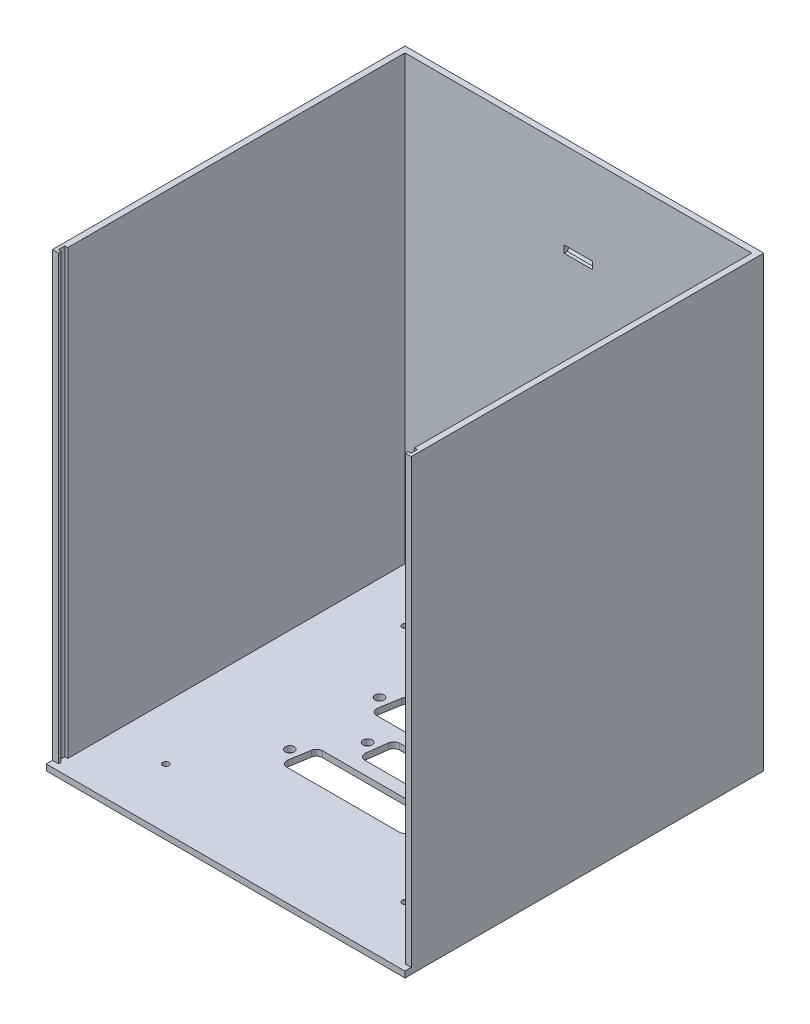
SolidWorks part; units mm, degrees
other "Markup1"
sketch "Sketch8" plane through (60, 0, -60) normal (0.7052, -0.7014, -0.1039) x (0.274, 0.4048, -0.8724)
other "Markup2"
sketch "Sketch9" plane through (60, 0, -60) normal (0.9922, -0.0018, -0.1244) x (-0.0942, 0.6423, -0.7606)
ref_plane "Front Plane" through (0, 0, 0) normal (0, 0, 1) x (1, 0, 0)
ref_plane "Top Plane" through (0, 0, 0) normal (0, 1, 0) x (1, 0, 0)
ref_plane "Right Plane" through (0, 0, 0) normal (1, 0, 0) x (0, 0, -1)
sketch "Sketch1" plane through (0, 0, 0) normal (0, 1, 0) x (1, 0, 0)
  line L5 (-60, 60) -> (60, 60)
  line L6 (-60, 60) -> (-60, -60)
  line L7 (-60, -60) -> (60, -60)
  line L8 (60, 60) -> (60, -60)
  dimension "D1" = 120
  dimension "D2" = 120
  dimension "D3" = 60
  dimension "D4" = 60
extrude "Main-Body" add sketch "Sketch1" along normal blind 150
sketch "Sketch11" plane through (0, 150, 0) normal (0, 1, 0) x (1, 0, 0)
  line L0 (-60, 60) -> (-60, -60) construction
  line L1 (58, -60) -> (-58, -60)
  line L2 (58, -60) -> (58, 58)
  line L3 (58, 58) -> (-58, 58)
  line L4 (-58, -60) -> (-58, 58)
  line L5 (58, -60) -> (-58, 58) construction
  line L6 (58, 58) -> (-58, -60) construction
  line L13 (60, 60) -> (-60, 60) construction
  point P0 (0, -1)
  dimension "D1" = 116
  dimension "D2" = 118
  dimension "D6" = 2
  dimension "D7" = 2
extrude "Hollow" cut sketch "Sketch11" against normal blind 148
sketch "Sketch12" plane through (0, 150, 0) normal (0, 1, 0) x (1, 0, 0)
  line L0 (-60, 60) -> (-60, -60) construction
  line L1 (-58, -60) -> (-60, -60)
  line L2 (-58, -60) -> (-58, -57.9)
  line L3 (-58, -57.9) -> (-60, -57.9)
  line L4 (-60, -60) -> (-60, -57.9)
  dimension "D1" = 2.1
extrude "Lid-Cut" cut sketch "Sketch12" against normal blind 148
mirror "Mirror-Lid-Cut" about plane through (0, 0, 0) normal (1, 0, 0) of "Lid-Cut"
sketch "Sketch13" plane through (0, 150, 0) normal (0, 1, 0) x (1, 0, 0)
  line L0 (-58, 58) -> (-58, -57.9) construction
  line L1 (-58, -57) -> (-59, -57)
  line L2 (-58, -57) -> (-58, -54.8)
  line L3 (-58, -54.8) -> (-59, -54.8)
  line L4 (-59, -57) -> (-59, -54.8)
  line L5 (-58, -57.9) -> (-60, -57.9) construction
  dimension "D1" = 1
  dimension "D2" = 0.9
  dimension "D3" = 2.2
extrude "Rail-Cut" cut sketch "Sketch13" against normal blind 148
mirror "Mirror-Rail-Cut" about plane through (0, 0, 0) normal (1, 0, 0) of "Rail-Cut"
sketch "Sketch2" plane through (0, 0, 0) normal (0, -1, 0) x (1, 0, 0)
  circle A0 centre (-40, 40) radius 1
  circle A1 centre (40, 40) radius 1
  circle A2 centre (40, -40) radius 1
  circle A3 centre (-40, -40) radius 1
  dimension "D1" = 40
  dimension "D3" = 2
  dimension "D2" = 40
  dimension "D4" = 2
  dimension "D5" = 2
extrude "Main-PCB-Holes" cut sketch "Sketch2" against normal up to next
sketch "Sketch4" plane through (0, 0, 0) normal (0, -1, 0) x (1, 0, 0)
  line L0 (-12.5, 0) -> (12.5, 0) construction
  line L1 (-23.52, -15) -> (23.52, -15) construction
  line L2 (-6.8916, -5.1179) -> (6.8916, -5.1179)
  line L4 (-7.7666, 5.6321) -> (7.7666, 5.6321)
  line L6 (-17.6522, -20.0462) -> (17.6522, -20.0462)
  line L8 (-18.7772, -9.2962) -> (18.7772, -9.2962)
  line L10 (-23.52, 15) -> (23.52, 15) construction
  line L11 (-17.6522, 9.9538) -> (17.6522, 9.9538)
  line L13 (-18.7772, 20.7038) -> (18.7772, 20.7038)
  line L16 (-19.625, 11.625) -> (-20.75, 18.375)
  line L19 (20.75, 18.375) -> (19.625, 11.625)
  line L22 (-8.875, -3.375) -> (-9.75, 3.375)
  line L25 (9.75, 3.375) -> (8.875, -3.375)
  line L28 (-20.75, -11.625) -> (-19.625, -18.375)
  line L31 (19.625, -18.375) -> (20.75, -11.625)
  circle A0 centre (-12.5, 0) radius 1.5
  circle A1 centre (12.5, 0) radius 1.5
  circle A2 centre (-23.52, -15) radius 1.5
  circle A3 centre (23.52, -15) radius 1.5
  circle A4 centre (-23.52, 15) radius 1.5
  circle A5 centre (23.52, 15) radius 1.5
  arc A6 (18.7772, 20.7038) -> (20.75, 18.375) centre (18.7772, 18.7038) cw
  arc A7 (-18.7772, 20.7038) -> (-20.75, 18.375) centre (-18.7772, 18.7038) ccw
  arc A8 (17.6522, 9.9538) -> (19.625, 11.625) centre (17.6522, 11.9538) ccw
  arc A9 (-17.6522, 9.9538) -> (-19.625, 11.625) centre (-17.6522, 11.9538) cw
  arc A10 (20.75, -11.625) -> (18.7772, -9.2962) centre (18.7772, -11.2962) ccw
  arc A11 (17.6522, -20.0462) -> (19.625, -18.375) centre (17.6522, -18.0462) ccw
  arc A12 (-19.625, -18.375) -> (-17.6522, -20.0462) centre (-17.6522, -18.0462) ccw
  arc A13 (-20.75, -11.625) -> (-18.7772, -9.2962) centre (-18.7772, -11.2962) cw
  arc A14 (7.7666, 5.6321) -> (9.75, 3.375) centre (7.7666, 3.6321) cw
  arc A15 (8.875, -3.375) -> (6.8916, -5.1179) centre (6.8916, -3.1179) cw
  arc A16 (-8.875, -3.375) -> (-6.8916, -5.1179) centre (-6.8916, -3.1179) ccw
  arc A17 (-9.75, 3.375) -> (-7.7666, 5.6321) centre (-7.7666, 3.6321) cw
  point P4 (0, 0)
  point P12 (0, 5.6321)
  point P17 (0, -15)
  point P24 (0, -20.0462)
  point P29 (0, 15)
  point P32 (0, -5.1179)
  point P34 (0, 9.9538)
  point P35 (0, 20.7038)
  point P36 (0, -9.2962)
  point P38 (20.1875, -15)
  point P41 (9.3125, 0)
  point P42 (20.1875, 15)
  point P52 (21.1381, 20.7038)
  point P59 (19.3465, 9.9538)
  point P66 (21.1381, -9.2962)
  point P69 (19.3465, -20.0462)
  point P76 (10.0426, 5.6321)
  point P79 (8.6491, -5.1179)
  dimension "D1" = 3
  dimension "D2" = 3
  dimension "D8" = 3
  dimension "D7" = 3
  dimension "D14" = 3
  dimension "D15" = 3
  dimension "D4" = 41.5
  dimension "D21" = 2
  dimension "D25" = 2
  dimension "D27" = 2
  dimension "D3" = 25
  dimension "D6" = 10.75
  dimension "D9" = 47.04
  dimension "D13" = 15
  dimension "D16" = 47.04
  dimension "D18" = 10.75
  dimension "D19" = 15
  dimension "D20" = 10.75
  dimension "D28" = 39.25
  dimension "D30" = 41.5
  dimension "D31" = 39.25
  dimension "D32" = 19.5
  dimension "D33" = 17.75
extrude "Connector-Slots" cut sketch "Sketch4" against normal up to next
sketch "Sketch14" plane through (0, 0, 0) normal (1, 0, 0) x (0, 0, -1)
  line L0 (58, 121) -> (60, 121)
  line L1 (58, 2) -> (58, 150) construction
  line L2 (60, 150) -> (60, 0) construction
  line L3 (60, 121) -> (60, 120.88)
  line L4 (60, 120.88) -> (60, 119.88)
  line L5 (60, 119.88) -> (59.8206, 119.88)
  line L6 (59.8206, 119.88) -> (59.07, 118.58)
  line L7 (59.07, 118.58) -> (58, 118.58)
  line L10 (60, 150) -> (-57.9, 150) construction
  line L11 (58, 121) -> (58, 118.58)
  dimension "D1" = 29
  dimension "D2" = 0.12
  dimension "D3" = 2.42
  dimension "D4" = 1
  dimension "D5" = 30
  dimension "D6" = 1.07
extrude "Cut-Extrude1" cut sketch "Sketch14" against normal mid plane 9.5
